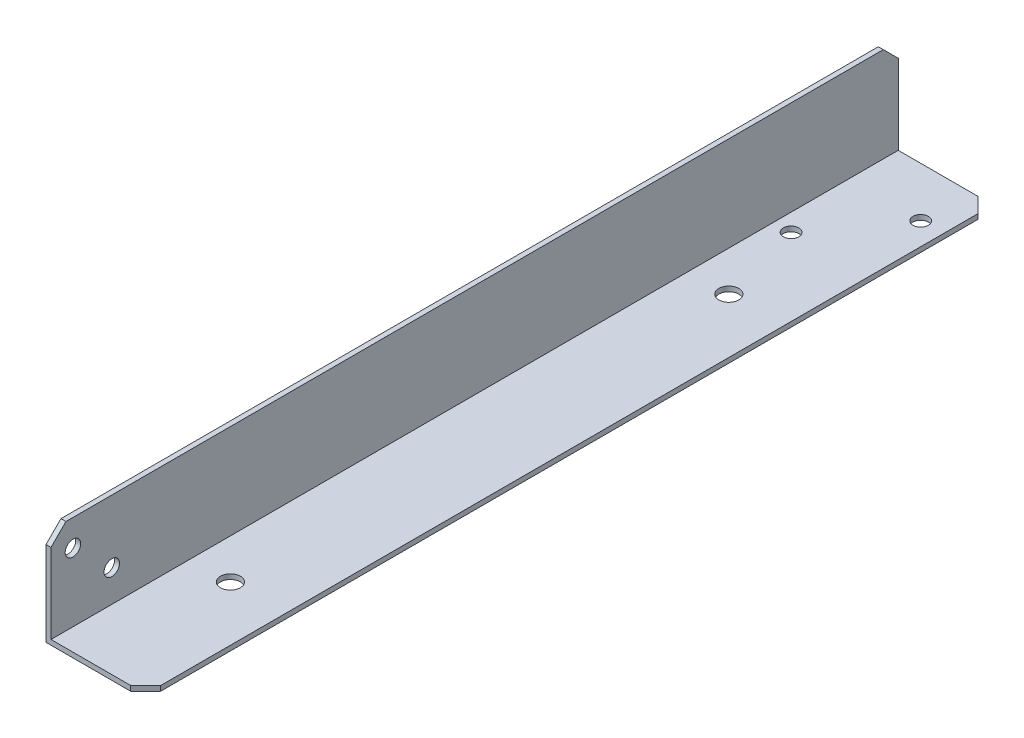
SolidWorks part; units mm, degrees
material "6063-T5"
ref_plane "Спереди" through (0, 0, 0) normal (0, 0, 1) x (1, 0, 0)
ref_plane "Сверху" through (0, 0, 0) normal (0, 1, 0) x (1, 0, 0)
ref_plane "Справа" through (0, 0, 0) normal (1, 0, 0) x (0, 0, -1)
sketch "Sketch1" plane through (0, 0, 0) normal (0, 0, 1) x (1, 0, 0)
  line L0 (0, 0) -> (20, 0)
  line L1 (20, 0) -> (20, 1)
  line L2 (20, 1) -> (1, 1)
  line L3 (1, 1) -> (1, 20)
  line L4 (1, 20) -> (0, 20)
  line L5 (0, 20) -> (0, 0)
  dimension "D1" = 20
  dimension "D2" = 20
  dimension "D3" = 1
  dimension "D4" = 1
extrude "Base" add sketch "Sketch1" along normal blind 170
chamfer "Chamfer1" distance 3 angle 45 4 edges at (20, 0.5, 170) (0.5, 20, 170) (0.5, 20, 0) (20, 0.5, 0)
sketch "Sketch4" plane through (2, 1, 0) normal (0, 1, 0) x (0, 0, -1)
  line L0 (-167, 2) -> (-3, 2) construction
  line L1 (0, -15) -> (0, 1) construction
  circle A0 centre (-10, -13.5) radius 1.55
  circle A1 centre (-25, -2.5) radius 1.55
  dimension "D5" = 3.1
  dimension "D6" = 3.1
  dimension "D1" = 4.5
  dimension "D2" = 15.5
  dimension "D3" = 10
  dimension "D4" = 25
extrude "CarriageSide" cut sketch "Sketch4" against normal through all
sketch "Sketch6" plane through (1, 0, 0) normal (1, 0, 0) x (0, 0, -1)
  line L1 (-170, 1) -> (-170, 17) construction
  line L2 (-170, 0) -> (0, 0) construction
  circle A0 centre (-165.6, 14.68) radius 1.55
  circle A1 centre (-157.8, 7.38) radius 1.55
  dimension "D5" = 3.1
  dimension "D1" = 7.8
  dimension "D2" = 7.38
  dimension "D3" = 7.3
  dimension "D4" = 4.4
extrude "CableChainSide" cut sketch "Sketch6" against normal up to surface (1 mm away) up to face at (0, 12.3333, 85)
sketch "Sketch7" plane through (0, 0, 0) normal (0, -1, 0) x (1, 0, 0)
  line L0 (0, 170) -> (0, 0) construction
  circle A0 centre (9, 142) radius 2
  circle A1 centre (9, 42) radius 2
  dimension "D1" = 4
  dimension "D2" = 9
  dimension "D3" = 100
  dimension "D4" = 42
extrude "Cut-Extrude1" cut sketch "Sketch7" against normal through all
equation "\"D2@Sketch1\"=\"D1@Sketch1\""
equation "\"D4@Sketch1\"=\"D3@Sketch1\""
